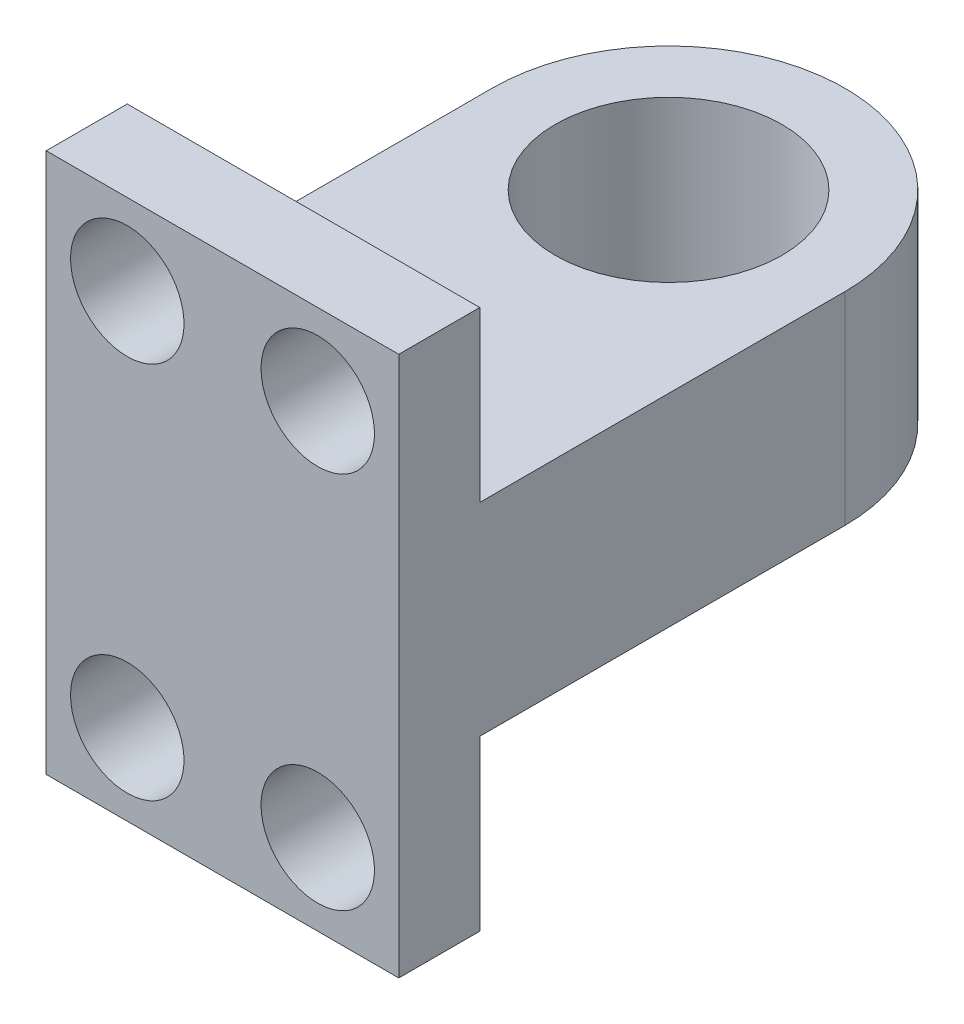
SolidWorks part; units mm, degrees
ref_plane "Front Plane" through (0, 0, 0) normal (0, 0, 1) x (1, 0, 0)
ref_plane "Top Plane" through (0, 0, 0) normal (0, 1, 0) x (1, 0, 0)
ref_plane "Right Plane" through (0, 0, 0) normal (1, 0, 0) x (0, 0, -1)
sketch "Sketch1" plane through (0, 0, 0) normal (0, 1, 0) x (1, 0, 0)
  line L1 (0, 0) -> (-13.0528, 0)
  line L2 (0, 0) -> (0, 6.9896)
  line L3 (0, 6.9896) -> (-13.0528, 6.9896)
  line L4 (-13.0528, 0) -> (-13.0528, 6.9896)
  line L5 (-13.0528, 20.0424) -> (0, 20.0424)
  line L6 (-13.0528, 20.0424) -> (-13.0528, 6.9896)
  line L7 (-13.0528, 6.9896) -> (0, 6.9896)
  line L8 (0, 20.0424) -> (0, 6.9896)
  circle A1 centre (-6.5264, 13.516) radius 6.5264
  circle A2 centre (-6.5264, 13.516) radius 4.2
  dimension "D1" = 8.4
extrude "Boss-Extrude1" add sketch "Sketch1" along normal blind 7.5 contours L4 L1 L2 L3 L7 | A1 L3 L8 | A1 L6 L7 | A1 A2 region at (-6.5264, 0, -3.4948) region at (-1.4578, 0, -8.4473) region at (-11.595, 0, -8.4473) region at (-11.0107, 0, -9.0316)
sketch "Sketch2" plane through (0, 0, 0) normal (0, 0, 1) x (1, 0, 0)
  line L0 (-6.5264, 13.75) -> (-6.5264, 7.5) construction
  line L1 (-13.0528, 13.75) -> (0, 13.75)
  line L2 (-13.0528, 13.75) -> (-13.0528, -6.25)
  line L3 (-13.0528, -6.25) -> (0, -6.25)
  line L4 (0, 13.75) -> (0, -6.25)
  line L5 (0, 7.5) -> (-13.0528, 7.5) construction
  line L6 (-6.5264, 0) -> (-6.5264, -6.25) construction
  line L7 (0, 0) -> (-13.0528, 0) construction
  line L8 (-13.0528, 7.5) -> (-13.0528, 0) construction
  dimension "D1" = 20
extrude "Boss-Extrude2" add sketch "Sketch2" along normal blind 3
hole_wizard "Tap Drill for M5x0.8 Tap1" positions "3DSketch2" profile "Sketch6" hole size "M5x0.8" standard "ANSI Metric" end condition through all
sketch3d "3DSketch2"
  line L0 (-3, 13.75, 0) -> (-3, -6.25, 0)
  line L1 (0, 13.75, 0) -> (-13.0528, 13.75, 0) construction
  line L2 (-13.0528, -6.25, 0) -> (0, -6.25, 0) construction
  line L5 (-10.0528, -6.25, 0) -> (-10.0528, 13.75, 0)
  line L8 (0, 10.75, 0) -> (-13.0528, 10.75, 0)
  line L9 (0, 7.5, 0) -> (0, 13.75, 0) construction
  line L10 (-13.0528, 13.75, 0) -> (-13.0528, 7.5, 0) construction
  line L13 (-13.0528, -3.25, 0) -> (0, -3.25, 0)
  line L14 (-13.0528, 0, 0) -> (-13.0528, -6.25, 0) construction
  line L15 (0, -6.25, 0) -> (0, 0, 0) construction
  point P0 (-3, 10.75, 0)
  point P2 (-10.0528, 10.75, 0)
  point P4 (-3, -3.25, 0)
  point P6 (-10.0528, -3.25, 0)
  point P36 (0, 0, 0)
  point P37 (0, 0, 0)
  dimension "D1" = 3
  dimension "D2" = 3
  dimension "D3" = 3
  dimension "D4" = 3
sketch "Sketch6" plane through (-3, 10.75, 0) normal (1, 0, 0) x (0, 1, 0)
  line L0 (0, 0) -> (0, 3)
  line L1 (0, 3) -> (2.1, 3)
  line L2 (2.1, 3) -> (2.1, 0)
  line L5 (2.1, 0) -> (0, 0)
  line L11 (0, -6.35) -> (0, 107.95) construction
  dimension "Thru Hole Dia." = 4.2
  dimension "Thru Hole Depth" = 3
